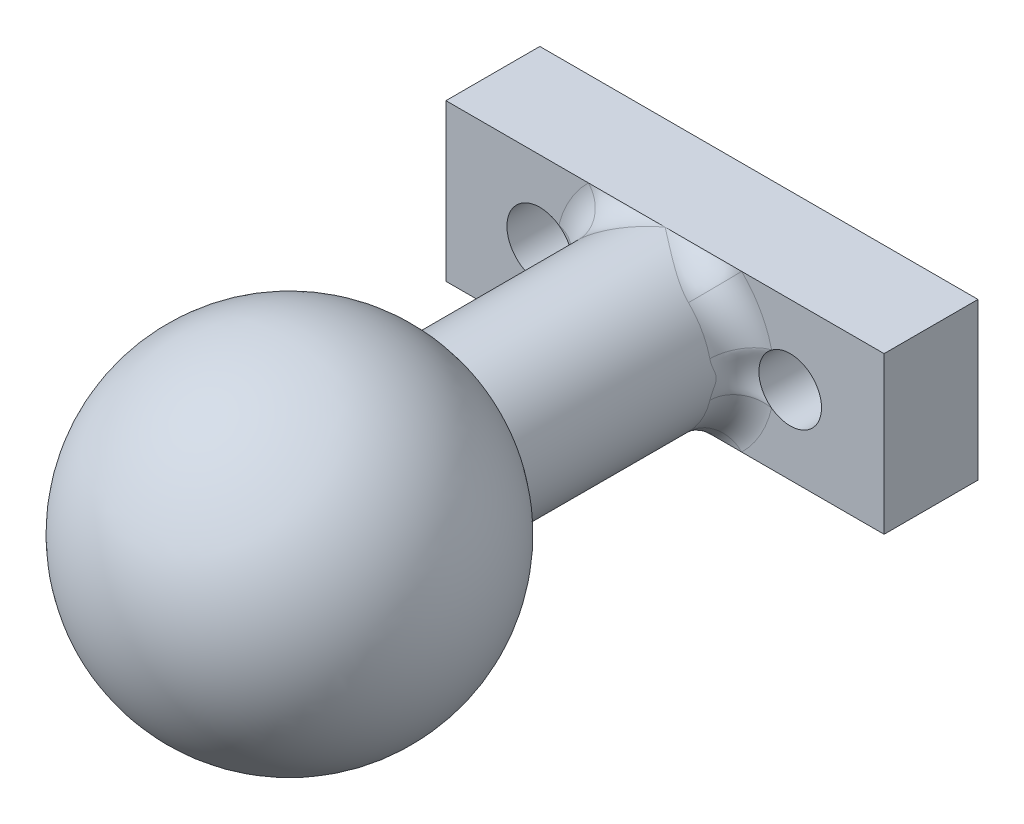
SolidWorks part; units mm, degrees
ref_plane "Front Plane" through (0, 0, 0) normal (0, 0, 1) x (1, 0, 0)
ref_plane "Top Plane" through (0, 0, 0) normal (0, 1, 0) x (1, 0, 0)
ref_plane "Right Plane" through (0, 0, 0) normal (1, 0, 0) x (0, 0, -1)
sketch "Sketch1" plane through (0, 0, 0) normal (0, 0, 1) x (1, 0, 0)
  circle A0 centre (0, 0) radius 2.5
extrude "Boss-Extrude1" add sketch "Sketch1" along normal blind 15
sketch "Sketch2" plane through (0, 0, 15) normal (0, 0, 1) x (1, 0, 0)
  line L0 (0, 5.5) -> (0, -5.5)
  arc A0 (0, 5.5) -> (0, -5.5) centre (0, 0) ccw
  dimension "D1" = 5.5
revolve "Revolve1" add sketch "Sketch2" angle 360 about L0
sketch "Sketch3" plane through (0, 0, 0) normal (0, 0, -1) x (-1, 0, 0)
  circle A0 centre (0, 0) radius 2
extrude "Boss-Extrude2" add sketch "Sketch3" against normal blind 10
sketch "Sketch4" plane through (0, 0, 0) normal (0, 0, -1) x (-1, 0, 0)
  line L1 (-7, 2.5) -> (7, 2.5)
  line L2 (-7, 2.5) -> (-7, -2.5)
  line L3 (-7, -2.5) -> (7, -2.5)
  line L4 (7, 2.5) -> (7, -2.5)
  line L5 (-7, 2.5) -> (7, -2.5) construction
  line L6 (-7, -2.5) -> (7, 2.5) construction
  point P0 (0, 0)
  dimension "D1" = 14
  dimension "D2" = 5
extrude "Boss-Extrude3" add sketch "Sketch4" against normal blind 3
sketch "Sketch5" plane through (0, 0, 0) normal (0, 0, -1) x (-1, 0, 0)
  line L0 (7, 2.5) -> (-7, 2.5) construction
  circle A0 centre (-4, 0) radius 1
  circle A1 centre (4, 0) radius 1.05
  dimension "D1" = 2.5
  dimension "D2" = 2.5
  dimension "D3" = 4
  dimension "D4" = 4
extrude "Cut-Extrude1" cut sketch "Sketch5" against normal blind 3
fillet "Fillet1" radius 1 2 edges at (2.5, 0, 3) (-2.5, 0, 3)
